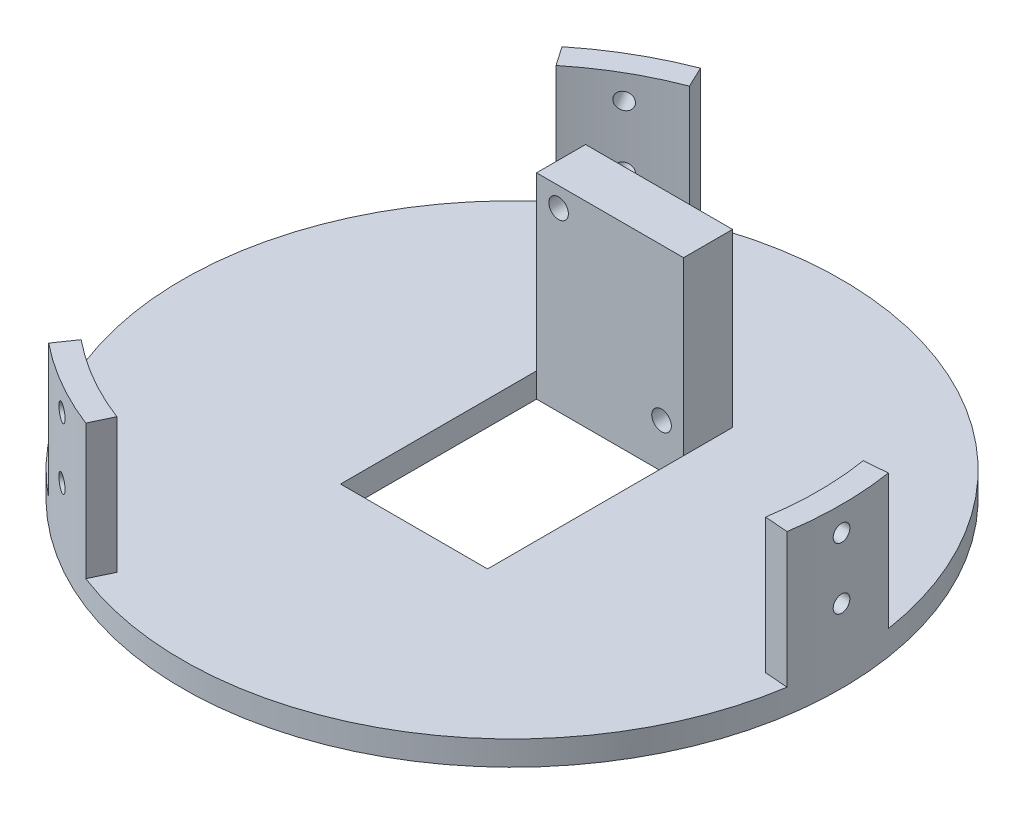
SolidWorks part; units mm, degrees
material "6061-T6 (SS)"
ref_plane "Front" through (0, 0, 0) normal (0, 0, 1) x (1, 0, 0)
ref_plane "Top" through (0, 0, 0) normal (0, 1, 0) x (1, 0, 0)
ref_plane "Right" through (0, 0, 0) normal (1, 0, 0) x (0, 0, -1)
sketch "Sketch1" plane through (0, 0, 0) normal (0, 1, 0) x (1, 0, 0)
  line L1 (0, 0) -> (127.635, 0)
  line L2 (0, 0) -> (0, 127.635)
  line L3 (0, 127.635) -> (127.635, 127.635)
  line L4 (127.635, 0) -> (127.635, 127.635)
  dimension "D1" = 127.635
  dimension "D2" = 127.635
extrude "Main Plate" add sketch "Sketch1" along normal blind 6.35
sketch "Sketch9" plane through (0, 6.35, 0) normal (0, 1, 0) x (1, 0, 0)
  circle A0 centre (63.8175, 63.8175) radius 85.725
  dimension "D1" = 171.45
extrude "Boss-Extrude1" add sketch "Sketch9" against normal up to surface (6.35 mm away) contours A0 up to face at (63.8175, 0, -63.8175)
sketch "Sketch10" plane through (0, 6.35, 0) normal (0, 1, 0) x (1, 0, 0)
  circle A0 centre (63.8175, 63.8175) radius 95.25
  circle A1 centre (63.8175, 63.8175) radius 85.4075
  dimension "D1" = 170.815
  dimension "D2" = 190.5
extrude "Cut-Extrude1" cut sketch "Sketch10" against normal blind 167.64 contours A0 | A1
sketch "Sketch14" plane through (0, 6.35, 0) normal (0, 1, 0) x (1, 0, 0)
  line L0 (201.1692, 63.8175) -> (-73.4523, 63.8175) construction
ref_plane "Plane1" through (0, 0, -63.8175) normal (0, 0, -1) x (-1, 0, 0)
ref_plane "Plane3" through (0, 3.175, 0) normal (0, 1, 0) x (1, 0, 0)
ref_plane "Plane2" through (-21.59, 0, 0) normal (-1, 0, 0) x (0, 0, 1)
sketch "Sketch18" plane through (0, 3.175, 0) normal (0, 1, 0) x (1, 0, 0)
  circle A0 centre (63.8175, 63.8175) radius 85.4075
  circle A1 centre (63.8175, 63.8175) radius 79.375
  circle A4 centre (63.8175, 63.8175) radius 85.4075 construction
  dimension "D1" = 158.75
extrude "Boss-Extrude2" add sketch "Sketch18" along normal blind 38.1
sketch "Sketch20" plane through (0, 6.35, 0) normal (0, 1, 0) x (1, 0, 0)
  line L0 (63.8175, 143.1925) -> (63.8175, -15.5575) construction
  line L1 (-15.5575, 63.8175) -> (143.1925, 63.8175) construction
  line L2 (63.8175, 63.8175) -> (-15.5575, -73.664) construction
  circle A0 centre (63.8175, 63.8175) radius 79.375 construction
  dimension "D1" = 30
ref_plane "Plane5" through (-15.5575, 6.35, 73.664) normal (-0.5, 0, 0.866) x (0.866, 0, 0.5)
sketch "Sketch15" plane through (166.2216, -6.35, 178.6143) normal (0.5, 0, -0.866) x (-0.866, 0, -0.5)
  line L3 (289.2754, 47.625) -> (130.5254, 47.625) construction
  circle A0 centre (209.9004, 25.4) radius 2.159
  circle A1 centre (209.9004, 41.275) radius 2.159
  dimension "D1" = 4.318
  dimension "D2" = 15.875
  dimension "D3" = 4.318
  dimension "D6" = 6.35
extrude "Cut-Extrude3" cut sketch "Sketch15" along normal blind 88.9
pattern_circular "CirPattern1" count 3 over 360 about axis through (63.8175, -161.29, -63.8175) along (0, 1, 0) of "Cut-Extrude3" reverse direction yes
ref_plane "Plane4" through (63.8175, 0, 0) normal (-1, 0, 0) x (0, 0, 1)
sketch "Sketch23" plane through (0, 6.35, 0) normal (0, 1, 0) x (1, 0, 0)
  line L0 (13.6787, 125.352) -> (7.5523, 134.2379)
  line L1 (15.1867, 11.8815) -> (13.6787, 2.283) construction
  line L3 (-15.5575, 63.8175) -> (143.1925, 63.8175) construction
  line L4 (63.8175, 143.1925) -> (63.8175, -15.5575) construction
  line L5 (-15.5575, 63.8175) -> (143.1925, 63.8175)
  line L6 (63.8175, 143.1925) -> (63.8175, -15.5575)
  line L7 (13.6787, 2.283) -> (6.9592, -7.4631)
  line L8 (-19.2671, 125.3206) -> (-48.797, 60.3978)
  line L9 (-48.797, 60.3978) -> (-9.8843, 7.0525)
  line L10 (-9.8843, 7.0525) -> (6.9592, -7.4631)
  line L11 (24.1345, -4.9259) -> (13.6787, 2.283) construction
  line L14 (7.5523, 134.2379) -> (-19.2671, 125.3206)
  line L15 (24.1345, 132.5609) -> (13.6787, 125.352) construction
  line L28 (63.8175, 63.8175) -> (24.1345, -4.9259) construction
  line L29 (63.8175, 63.8175) -> (24.1345, 132.5609) construction
  line L30 (142.1773, 76.4717) -> (152.9359, 77.3344)
  line L31 (152.9359, 77.3344) -> (158.6231, 105.0193)
  line L32 (158.6231, 105.0193) -> (117.1632, 163.0543)
  line L33 (117.1632, 163.0543) -> (51.5085, 156.0277)
  line L34 (51.5085, 156.0277) -> (30.5159, 148.6985)
  line L35 (35.5964, 138.0062) -> (30.5159, 148.6985)
  line L36 (35.5964, -10.3712) -> (30.9643, -20.1198)
  line L37 (30.9643, -20.1198) -> (52.0965, -38.8874)
  line L38 (52.0965, -38.8874) -> (123.0863, -31.9996)
  line L39 (123.0863, -31.9996) -> (149.8284, 28.3723)
  line L40 (149.8284, 28.3723) -> (153.9775, 50.217)
  line L41 (142.1773, 51.1633) -> (153.9775, 50.217)
  circle A0 centre (63.8175, 63.8175) radius 79.375 construction
  arc A1 (13.6787, 2.283) -> (13.6787, 125.352) centre (63.8175, 63.8175) cw
  circle A3 centre (63.8175, 63.8175) radius 79.375
  arc A6 (35.5964, 138.0062) -> (142.1773, 76.4717) centre (63.8175, 63.8175) cw
  arc A7 (142.1773, 51.1633) -> (35.5964, -10.3712) centre (63.8175, 63.8175) cw
  circle A9 centre (63.8175, 63.8175) radius 79.375
  circle M15 centre (63.8175, 63.8175) radius 79.375
  dimension "D1" = 79.375
  dimension "D2" = 0
  dimension "D3" = 12.7
  dimension "D4" = 90
  dimension "D5" = 12.7
  dimension "D6" = 90
  dimension "D8" = 60.004
  dimension "D9" = 60.004
  dimension "D7" = 3
extrude "Cut-Extrude6" cut sketch "Sketch23" along normal blind 111.6 contours L9 L10 L7 L8 M15 | L34 L35 A6 L30 L31 L32 L33 | L40 L41 A7 L36 L37 L38 L39 region at (-18.2379, 6.35, -69.3048)
sketch "Sketch24" plane through (0, 6.35, 0) normal (0, 1, 0) x (1, 0, 0)
  line L1 (44.7675, 89.2175) -> (82.8675, 89.2175)
  line L2 (44.7675, 89.2175) -> (44.7675, 38.4175)
  line L3 (44.7675, 38.4175) -> (82.8675, 38.4175)
  line L4 (82.8675, 89.2175) -> (82.8675, 38.4175)
  line L5 (44.7675, 89.2175) -> (82.8675, 38.4175) construction
  line L6 (44.7675, 38.4175) -> (82.8675, 89.2175) construction
  arc A0 (148.2085, 76.9553) -> (32.9997, 143.4712) centre (63.8175, 63.8175) ccw construction
  arc A1 (148.2085, 76.9553) -> (32.9997, 143.4712) centre (63.8175, 63.8175) ccw
  point P0 (63.8175, 63.8175)
  point P8 (0, 0)
  dimension "D1" = 50.8
  dimension "D2" = 38.1
extrude "Cut-Extrude7" cut sketch "Sketch24" against normal through all contours L4 L1 L2 L3 region at (63.8175, 6.35, -63.8175)
sketch "Sketch25" plane through (0, 6.35, 0) normal (0, 1, 0) x (1, 0, 0)
  line L1 (44.7675, 101.9175) -> (82.8675, 101.9175)
  line L2 (44.7675, 101.9175) -> (44.7675, 89.2175)
  line L3 (44.7675, 89.2175) -> (82.8675, 89.2175)
  line L4 (82.8675, 101.9175) -> (82.8675, 89.2175)
  line L5 (44.7675, 101.9175) -> (82.8675, 89.2175) construction
  line L6 (44.7675, 89.2175) -> (82.8675, 101.9175) construction
  point P0 (63.8175, 95.5675)
  dimension "D1" = 12.7
extrude "Boss-Extrude3" add sketch "Sketch25" along normal blind 44.45
sketch "Sketch26" plane through (0, 0, -89.2175) normal (0, 0, 1) x (1, 0, 0)
  line L0 (44.7675, 50.8) -> (44.7675, 6.35) construction
  line L1 (44.7675, 50.8) -> (82.8675, 50.8) construction
  circle A0 centre (50.4825, 45.72) radius 2.54
  circle A1 centre (77.1525, 11.43) radius 2.54
  dimension "D1" = 5.08
  dimension "D2" = 5.715
  dimension "D3" = 34.29
  dimension "D4" = 5.08
  dimension "D5" = 26.67
extrude "Cut-Extrude8" cut sketch "Sketch26" against normal blind 44.45
